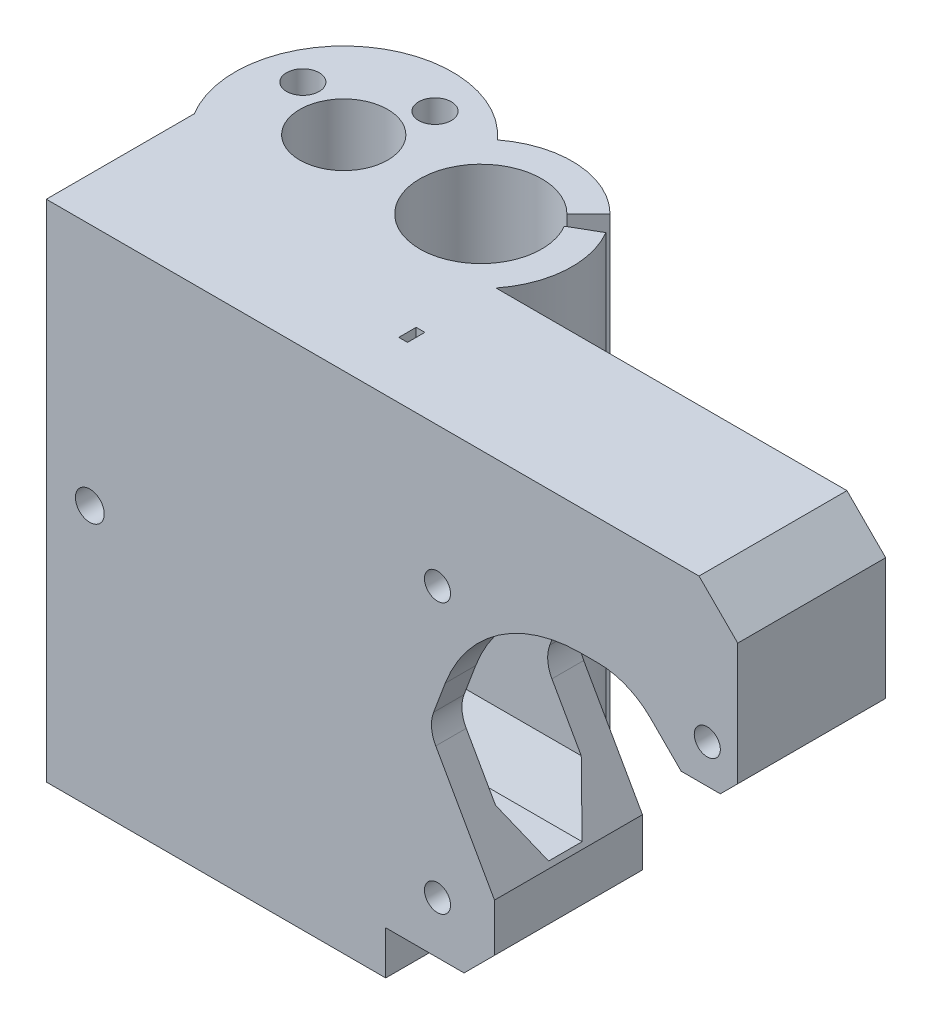
SolidWorks part; units mm, degrees
ref_plane "Front Plane" through (0, 0, 0) normal (0, 0, 1) x (1, 0, 0)
ref_plane "Top Plane" through (0, 0, 0) normal (0, 1, 0) x (1, 0, 0)
ref_plane "Right Plane" through (0, 0, 0) normal (1, 0, 0) x (0, 0, -1)
sketch "Sketch1" plane through (0, 0, 0) normal (0, 0, 1) x (1, 0, 0)
  line L0 (39, -53) -> (48, -53)
  line L1 (0, 0) -> (39, 0)
  line L2 (0, 0) -> (0, -58)
  line L3 (0, -58) -> (39, -58)
  line L4 (39, -53) -> (39, -58)
  line L5 (39, 0) -> (75, 0)
  line L6 (75, 0) -> (79.45, -4.45)
  line L7 (79.45, -4.45) -> (79.45, -18.45)
  line L8 (79.45, -18.45) -> (77.45, -20.45)
  line L9 (77.45, -20.45) -> (72.95, -20.45)
  line L10 (72.95, -20.45) -> (69.45, -16.95)
  line L12 (45.8405, -25.2376) -> (44.5009, -28.8048)
  line L13 (44.75, -32.0294) -> (51.5, -44)
  line L14 (51.5, -44) -> (51.5, -49.5)
  line L15 (61.4145, -14.45) -> (63.4145, -14.45)
  line L16 (51.5, -49.5) -> (48, -53)
  arc A5 (63.4145, -14.45) -> (69.45, -16.95) centre (63.4145, -22.9855) cw
  arc A6 (61.4145, -14.45) -> (45.8405, -25.2376) centre (61.4145, -31.0859) ccw
  arc A7 (44.5009, -28.8048) -> (44.75, -32.0294) centre (48.083, -30.15) ccw
  dimension "D1" = 58
  dimension "D2" = 39
  dimension "D3" = 75
  dimension "D4" = 4.45
  dimension "D5" = 135
  dimension "D6" = 14
  dimension "D7" = 2
  dimension "D8" = 3.5
  dimension "D9" = 6
  dimension "D10" = 5
  dimension "D11" = 4.5
  dimension "D12" = 130
  dimension "D13" = 3.5
  dimension "D14" = 5.5
  dimension "D15" = 6.75
  dimension "D16" = 9
  dimension "D17" = 13.85
  dimension "D18" = 3.417
  dimension "D19" = 2
extrude "Boss-Extrude1" add sketch "Sketch1" along normal blind 17
sketch "Sketch2" plane through (0, 0, 0) normal (0, 1, 0) x (1, 0, 0)
  line L0 (0, -17) -> (0, 6.5) construction
  line L1 (0, 6.5) -> (26.427, 6.5) construction
  circle A0 centre (26.427, 6.5) radius 10.5
  dimension "D2" = 21
  dimension "D1" = 23.5
  dimension "D3" = 26.427
extrude "Boss-Extrude2" add sketch "Sketch2" against normal up to surface (58 mm away) up to face at (19.5, -58, 8.5)
sketch "Sketch3" plane through (0, 0, 0) normal (0, 1, 0) x (1, 0, 0)
  line L0 (0, -17) -> (0, 20.4292) construction
  line L1 (10.6771, 6.5) -> (0, 6.5) construction
  line L2 (75, -17) -> (0, -17) construction
  circle A0 centre (10.6771, 6.5) radius 12.5
  dimension "D3" = 25
  dimension "D2" = 23.5
extrude "Boss-Extrude3" add sketch "Sketch3" against normal blind 13.5
sketch "Sketch4" plane through (0, 0, 0) normal (0, 1, 0) x (1, 0, 0)
  circle A0 centre (26.427, 6.5) radius 7
  circle A1 centre (10.6771, 6.5) radius 5.05
  dimension "D1" = 10.1
  dimension "D2" = 14
extrude "Cut-Extrude1" cut sketch "Sketch4" against normal through all
sketch "Sketch5" plane through (0, 0, 0) normal (-1, 0, 0) x (0, 0, 1)
  line L0 (10.5, -43.5) -> (6.65, -43.5)
  line L1 (6.65, -43.5) -> (3.65, -38)
  line L2 (3.65, -38) -> (3.65, -19)
  line L3 (3.65, -19) -> (6.65, -16)
  line L4 (6.65, -16) -> (10.5, -16)
  line L5 (10.5, -16) -> (13.5, -19)
  line L6 (13.5, -19) -> (13.5, -38)
  line L7 (13.5, -38) -> (10.5, -43.5)
  line L8 (17, 0) -> (0, 0) construction
  line L9 (17, 0) -> (17, -58) construction
  circle A0 centre (8.5, -6) radius 4.05
  circle A1 centre (8.5, -51) radius 4.05
  dimension "D8" = 8.1
  dimension "D9" = 8.1
  dimension "D1" = 19
  dimension "D2" = 3
  dimension "D3" = 3.85
  dimension "D4" = 16
  dimension "D5" = 6
  dimension "D6" = 51
  dimension "D7" = 5.5
  dimension "D10" = 3
  dimension "D11" = 3
  dimension "D12" = 19
  dimension "D13" = 3.85
  dimension "D14" = 3
  dimension "D15" = 3
  dimension "D16" = 3.5
  dimension "D17" = 8.5
  dimension "D18" = 8.5
extrude "Cut-Extrude2" cut sketch "Sketch5" against normal blind 35
sketch "Sketch6" plane through (0, 0, 0) normal (0, 0, -1) x (-1, 0, 0)
  line L0 (-75.9503, -16.0252) -> (-44.9503, -16.0252) construction
  line L1 (-44.9503, -16.0252) -> (-44.9503, -47.0252) construction
  line L2 (-44.9503, -47.0252) -> (-75.9503, -47.0252) construction
  line L3 (-75.9503, -47.0252) -> (-75.9503, -16.0252) construction
  line L4 (-75.9503, -31.5252) -> (-44.9503, -31.5252) construction
  line L5 (-60.4503, -16.0252) -> (-60.4503, -47.0252) construction
  circle A0 centre (-75.9503, -16.0252) radius 1.5
  circle A1 centre (-44.9503, -16.0252) radius 1.5
  circle A2 centre (-44.9503, -47.0252) radius 1.5
  circle A3 centre (-60.4503, -31.5252) radius 11 construction
  point P14 (-60.4503, -31.5252)
  dimension "D3" = 22
  dimension "D4" = 3
  dimension "D1" = 31
  dimension "D2" = 31
extrude "Cut-Extrude3" cut sketch "Sketch6" against normal through all
sketch "Sketch8" plane through (35, 0, 0) normal (-1, 0, 0) x (0, 0, 1)
  line L8 (10.5, -43.5) -> (13.5, -38)
  line L9 (13.5, -38) -> (13.5, -19)
  line L10 (13.5, -19) -> (10.5, -16)
  line L11 (10.5, -16) -> (6.65, -16)
  line L12 (6.65, -16) -> (3.65, -19)
  line L13 (3.65, -19) -> (3.65, -38)
  line L14 (3.65, -38) -> (6.65, -43.5)
  line L15 (6.65, -43.5) -> (10.5, -43.5)
  line L16 (10.5, -43.5) -> (13.5, -38)
  line L17 (13.5, -38) -> (13.5, -19)
  line L18 (13.5, -19) -> (10.5, -16)
  line L19 (10.5, -16) -> (6.65, -16)
  line L20 (6.65, -16) -> (3.65, -19)
  line L21 (3.65, -19) -> (3.65, -38)
  line L22 (3.65, -38) -> (6.65, -43.5)
  line L23 (6.65, -43.5) -> (10.5, -43.5)
  dimension "D1" = 0
extrude "Cut-Extrude4" cut sketch "Sketch8" against normal blind 20
sketch "Sketch9" plane through (0, 0, 0) normal (0, 1, 0) x (1, 0, 0)
  line L0 (32.4461, 10.0735) -> (35.4774, 11.8236)
  line L1 (31.3767, 11.4497) -> (33.8516, 13.9246)
  line L2 (26.427, 6.5) -> (36.927, 6.5) construction
  line L3 (32.4461, 10.0735) -> (26.427, 6.5) construction
  line L4 (26.427, 6.5) -> (31.3767, 11.4497) construction
  arc A0 (32.4461, 10.0735) -> (31.3767, 11.4497) centre (26.427, 6.5) ccw
  arc A1 (35.4774, 11.8236) -> (33.8516, 13.9246) centre (26.427, 6.5) ccw
  arc A2 (34.6732, 0) -> (20.0124, 14.8128) centre (26.427, 6.5) ccw construction
  circle A3 centre (26.427, 6.5) radius 7 construction
  dimension "D1" = 15
  dimension "D2" = 30
extrude "Cut-Extrude5" cut sketch "Sketch9" against normal through all
sketch "Sketch10" plane through (0, 0, 0) normal (0, 1, 0) x (1, 0, 0)
  line L0 (13.5702, 14.0925) -> (10.6771, 6.5) construction
  line L1 (10.6771, 6.5) -> (3.0846, 9.3931) construction
  circle A0 centre (13.5702, 14.0925) radius 1.875
  circle A1 centre (3.0846, 9.3931) radius 1.875
  dimension "D3" = 3.75
  dimension "D4" = 3.75
  dimension "D1" = 90
  dimension "D2" = 8.125
  dimension "D5" = 8.125
extrude "Cut-Extrude6" cut sketch "Sketch10" against normal through all
sketch "Sketch11" plane through (0, -58, 0) normal (0, -1, 0) x (1, 0, 0)
  line L0 (0, 17) -> (0, 0) construction
  line L1 (35, 8.5) -> (34, 8.5)
  line L2 (35, 8.5) -> (35, 10.5)
  line L3 (35, 10.5) -> (34, 10.5)
  line L4 (34, 8.5) -> (34, 10.5)
  line L5 (0, 17) -> (39, 17) construction
  dimension "D1" = 35
  dimension "D2" = 1
  dimension "D3" = 2
  dimension "D4" = 6.5
extrude "Cut-Extrude7" cut sketch "Sketch11" against normal blind 8
ref_plane "Plane1" through (0, -29, 0) normal (0, 1, 0) x (1, 0, 0)
mirror "Mirror1" about plane through (0, -29, 0) normal (0, 1, 0) of "Cut-Extrude7"
sketch "Sketch12" plane through (0, 0, 17) normal (0, 0, 1) x (1, 0, 0)
  line L0 (0, 0) -> (0, -58) construction
  line L2 (75, 0) -> (0, 0) construction
  circle A0 centre (5, -28) radius 1.6588
  dimension "D1" = 3.3175
  dimension "D2" = 5
  dimension "D3" = 28
extrude "Cut-Extrude8" cut sketch "Sketch12" against normal through all
